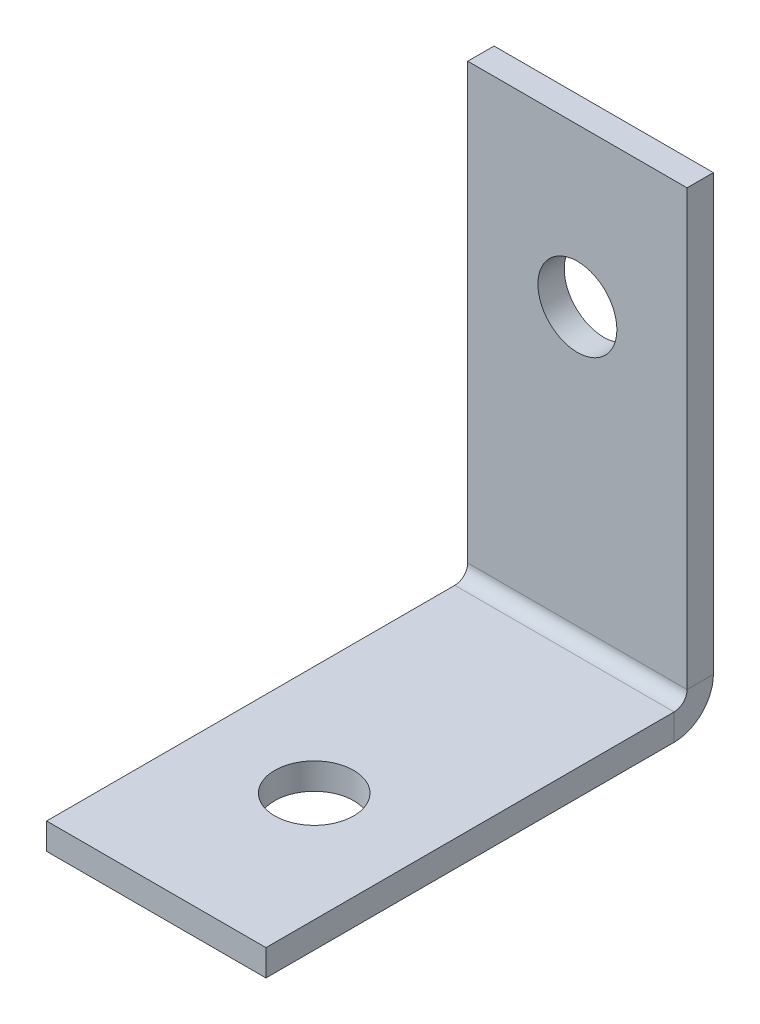
SolidWorks part; units mm, degrees
note: The reader was unsure of these and kept them because the rebuilt part matched: flange length of "邊線-凸緣1".
ref_plane "前基準面" through (0, 0, 0) normal (0, 0, 1) x (1, 0, 0)
ref_plane "上基準面" through (0, 0, 0) normal (0, 1, 0) x (1, 0, 0)
ref_plane "右基準面" through (0, 0, 0) normal (1, 0, 0) x (0, 0, -1)
sketch "草圖1" plane through (0, 0, 0) normal (0, 1, 0) x (1, 0, 0)
  line L1 (-6.25, 12.75) -> (6.25, 12.75)
  line L2 (-6.25, 12.75) -> (-6.25, -12.75)
  line L3 (-6.25, -12.75) -> (6.25, -12.75)
  line L4 (6.25, 12.75) -> (6.25, -12.75)
  line L5 (-6.25, 12.75) -> (6.25, -12.75) construction
  line L6 (-6.25, -12.75) -> (6.25, 12.75) construction
  point P0 (0, 0)
  dimension "D1" = 25.5
  dimension "D2" = 12.5
sheet metal parameters "鈑金1" thickness 1.5 parameters "D1"=0.7366, "厚度"=1.5
base flange "基材-凸緣1" sketch "草圖1" thickness 1.5 reverse thickness direction yes parameters "D1"=0.7366
edge flange "邊線-凸緣1" sketch "草圖5" flange angle 90 flange length 25.5 flange position material inside bend radius 0.7366 thickness 1.5 relief rectangular parameters "D6"=10
sketch "草圖5" plane through (0, 1.5, -12.75) normal (0, 0, -1) x (-1, 0, 0)
  line L2 (-6.25, 0) -> (-6.25, 25.5)
  line L3 (-6.25, 25.5) -> (6.25, 25.5)
  line L4 (6.25, 25.5) -> (6.25, 0)
  line L5 (-6.25, 0) -> (6.25, 0) construction
  line L6 (-6.25, 0) -> (6.25, 0)
bend "邊線彎折1" bend radius 0.7366 bend angle 90 parameters "D5"=1
sketch "草圖6" plane through (0, 1.5, 0) normal (0, 1, 0) x (1, 0, 0)
  line L0 (-6.25, -12.75) -> (6.25, -12.75) construction
  line L1 (0, -3.75) -> (0, 0) construction
  circle A0 centre (0, -3.75) radius 2.25
  dimension "D2" = 4.5
  dimension "D1" = 9
extrude "伸長1" cut sketch "草圖6" against normal blind 10 normal cut yes
sketch "草圖7" plane through (0, 0, -11.25) normal (0, 0, 1) x (1, 0, 0)
  line L0 (-6.25, 27) -> (6.25, 27) construction
  line L1 (0, 18) -> (0, 0) construction
  circle A0 centre (0, 18) radius 2.25
  dimension "D1" = 4.5
  dimension "D2" = 9
extrude "伸長2" cut sketch "草圖7" against normal blind 10 normal cut yes
flat pattern "平板-型式1" [suppressed]
sketch "彎折-線1" plane through (0, 0, 0) normal (0, 1, 0) x (-1, 0, 0)
bend of the flat pattern "平板-<邊線彎折1>1"
